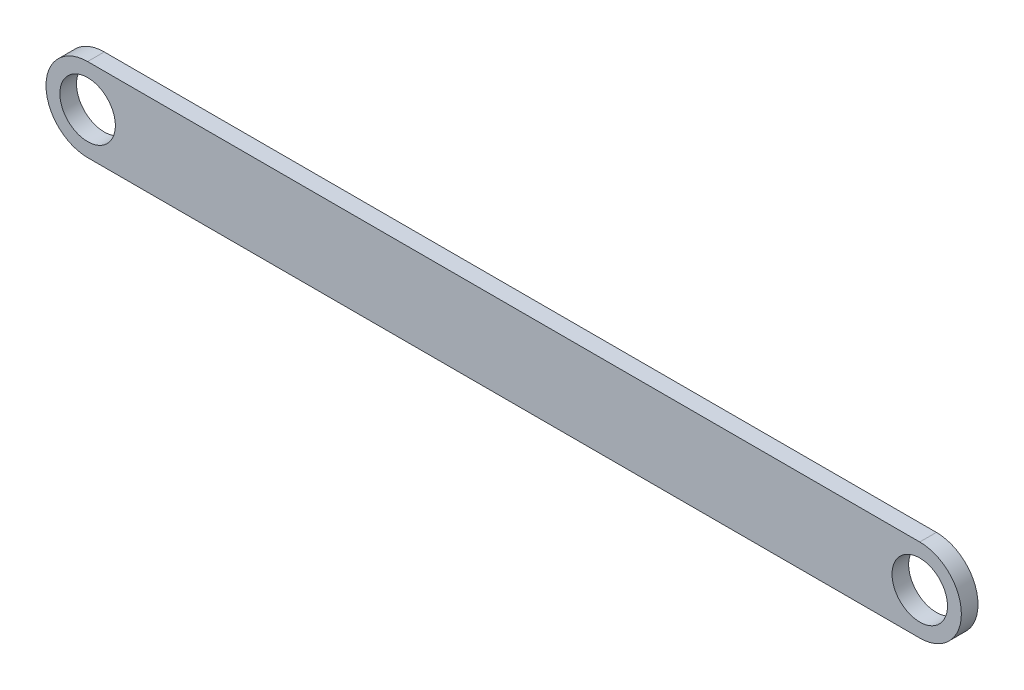
SolidWorks part; units mm, degrees
material "Acrylic (Medium-high impact)"
ref_plane "Front Plane" through (0, 0, 0) normal (0, 0, 1) x (1, 0, 0)
ref_plane "Top Plane" through (0, 0, 0) normal (0, 1, 0) x (1, 0, 0)
ref_plane "Right Plane" through (0, 0, 0) normal (1, 0, 0) x (0, 0, -1)
sketch "Sketch1" plane through (0, 0, 0) normal (0, 0, 1) x (1, 0, 0)
  line L0 (75, 0) -> (-75, 0) construction
  line L1 (75, -7.5) -> (-75, -7.5)
  line L2 (75, 7.5) -> (-75, 7.5)
  line L3 (0, 7.5) -> (0, -7.5) construction
  arc A0 (75, -7.5) -> (75, 7.5) centre (75, 0) ccw
  arc A1 (-75, 7.5) -> (-75, -7.5) centre (-75, 0) ccw
  circle A2 centre (75, 0) radius 5
  circle A3 centre (-75, 0) radius 5
  point P2 (0, 0)
  point P14 (19, 0)
  point P15 (-14, 0)
  point P16 (0, 3.5)
  point P17 (0, -3.5)
  point P30 (0, 3.5)
  point P33 (0, -3.5)
  dimension "D2" = 10
  dimension "D1" = 150
  dimension "D3" = 15
  dimension "D4" = 19
  dimension "D5" = 14
  dimension "D6" = 3.5
  dimension "D7" = 3.5
extrude "Boss-Extrude1" add sketch "Sketch1" along normal blind 3
